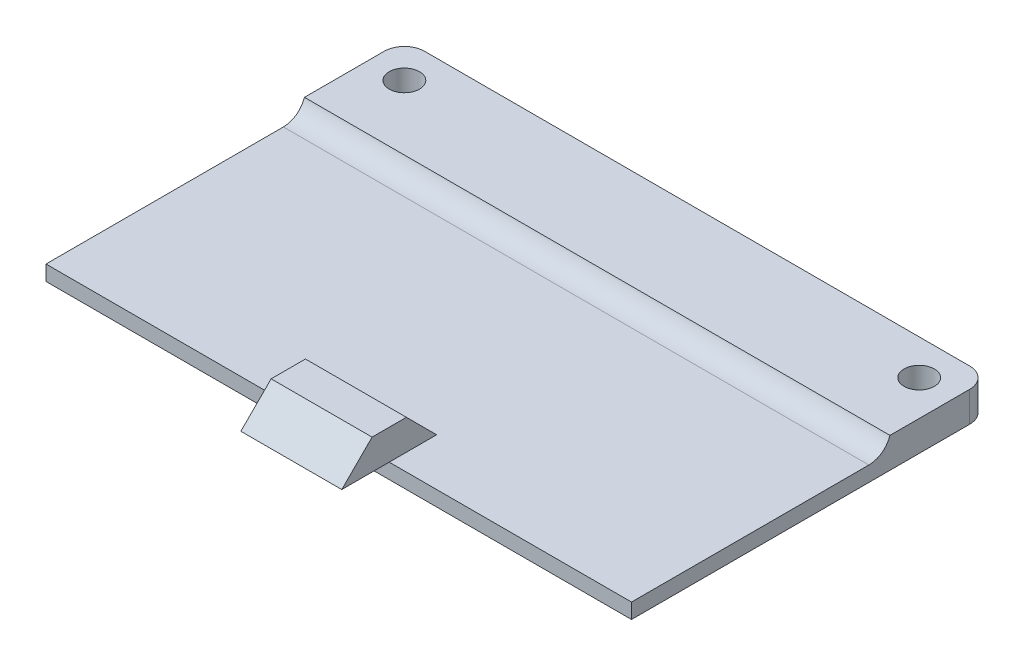
SolidWorks part; units mm, degrees
ref_plane "Front Plane" through (0, 0, 0) normal (0, 0, 1) x (1, 0, 0)
ref_plane "Top Plane" through (0, 0, 0) normal (0, 1, 0) x (1, 0, 0)
ref_plane "Right Plane" through (0, 0, 0) normal (1, 0, 0) x (0, 0, -1)
sketch "Sketch1" plane through (0, 0, 0) normal (0, 1, 0) x (1, 0, 0)
  line L0 (0, 0) -> (0, 49.8134) construction
  line L1 (-29, -17.75) -> (29, -17.75)
  line L2 (-29, -17.75) -> (-29, 17.75)
  line L3 (-29, 17.75) -> (29, 17.75)
  line L4 (29, -17.75) -> (29, 17.75)
  line L5 (-29, -17.75) -> (29, 17.75) construction
  line L6 (-29, 17.75) -> (29, -17.75) construction
  circle A0 centre (-25.5, 14.25) radius 1.5
  circle A2 centre (-25.5, 14.25) radius 3.5 construction
  circle A3 centre (25.5, 14.25) radius 1.5
  point P0 (0, 0)
  dimension "D1" = 3
  dimension "D5" = 7
  dimension "D3" = 35.5
  dimension "D4" = 58
extrude "Boss-Extrude1" add sketch "Sketch1" along normal blind 1.5
sketch "Sketch2" plane through (0, 1.5, 0) normal (0, 1, 0) x (1, 0, 0)
  line L0 (29, -17.75) -> (29, 17.75) construction
  line L1 (-29, 17.75) -> (29, 17.75)
  line L2 (-29, 17.75) -> (-29, 7.85)
  line L3 (-29, 7.85) -> (29, 7.85)
  line L4 (29, 17.75) -> (29, 7.85)
  line L5 (0, 0) -> (0, -24.499) construction
  line L6 (-29, -17.75) -> (29, -17.75) construction
  line L7 (-5, -22.45) -> (5, -22.45)
  line L8 (-5, -22.45) -> (-5, -13.05)
  line L9 (-5, -13.05) -> (5, -13.05)
  line L10 (5, -22.45) -> (5, -13.05)
  line L11 (-5, -22.45) -> (5, -13.05) construction
  line L12 (-5, -13.05) -> (5, -22.45) construction
  circle A0 centre (-25.5, 14.25) radius 1.5
  circle A1 centre (25.5, 14.25) radius 1.5
  point P16 (0, -17.75)
  line M5 (29, -17.75) -> (29, 17.75)
  line M6 (29, 17.75) -> (-29, 17.75)
  line M7 (-29, 17.75) -> (-29, -17.75)
  line M8 (-29, -17.75) -> (29, -17.75)
  circle M9 centre (-25.5, 14.25) radius 1.5
  circle M10 centre (25.5, 14.25) radius 1.5
  dimension "D1" = 9.9
  dimension "D2" = 4.7
  dimension "D3" = 10
extrude "Boss-Extrude3" add sketch "Sketch2" along normal blind 1.5 contours L3 M7 M5 M6 M9 M10 region at (0, 1.5, -12.7634)
fillet "Fillet1" radius 2.2 1 edges at (0, 1.5, -7.85)
extrude "Boss-Extrude4" add sketch "Sketch2<3>" along normal blind 3 contours L7 L10 L8 M8 | L10 L9 L8 M8 region at (0, 1.5, 20.1) region at (0, 1.5, 15.4)
sketch "Sketch2<3>" plane through (0, 1.5, 0) normal (0, 1, 0) x (1, 0, 0) same geometry as "Sketch2"
chamfer "Chamfer1" distance 3 angle 45 2 edges at (0, 4.5, 13.05) (0, 4.5, 22.45)
fillet "Fillet2" radius 2 2 edges at (29, 1.5, -17.75) (-29, 1.5, -17.75)
